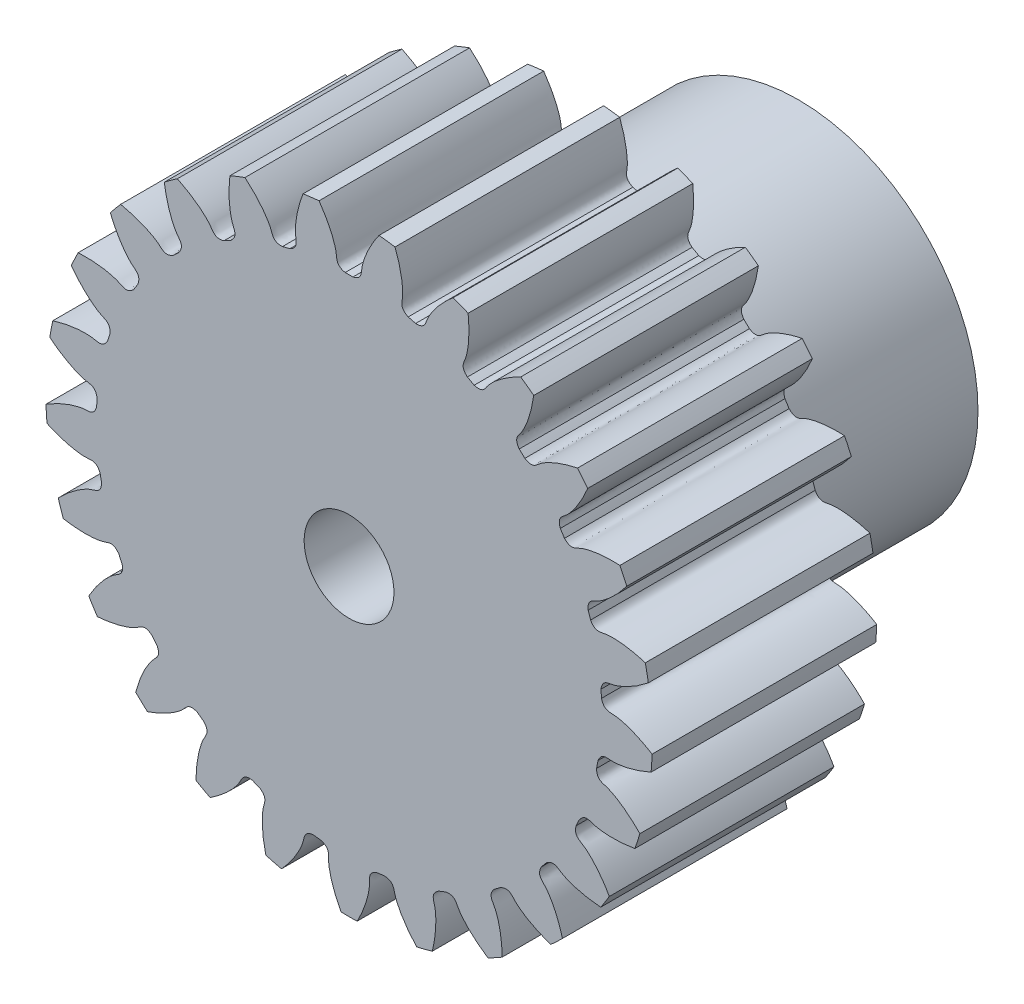
SolidWorks part; units mm, degrees
ref_plane "前视基准面" through (0, 0, 0) normal (0, 0, 1) x (1, 0, 0)
ref_plane "上视基准面" through (0, 0, 0) normal (0, 1, 0) x (1, 0, 0)
ref_plane "右视基准面" through (0, 0, 0) normal (1, 0, 0) x (0, 0, -1)
sketch "草图1" plane through (0, 0, 0) normal (0, 0, 1) x (1, 0, 0)
  circle A0 centre (0, 0) radius 6.75
extrude "凸台-拉伸1" add sketch "草图1" along normal blind 5
ref_axis "基准轴1" through (0, 0, 5) along (0, 0, -1)
sketch "草图2" plane through (0, 0, 0) normal (0, 0, 1) x (1, 0, 0)
  line L0 (0, 0) -> (0, 6.75) construction
  circle A0 centre (0, 0) radius 6.75 construction
  arc A1 (0.086, 5.6243) -> (-0.086, 5.6243) centre (0, 0) ccw
  arc A2 (1.6026, 7.6574) -> (-1.6026, 7.6574) centre (0, 0) ccw
  spline S0 degree 3 poles (0.086, 5.6243) (0.2867, 5.6675) (0.2678, 5.7886) (0.2871, 5.909) (0.2898, 5.9241) (0.2933, 5.9413) (0.2976, 5.9608) (0.3029, 5.9825) (0.3092, 6.0064) (0.3166, 6.0323) (0.3253, 6.0604) (0.3352, 6.0905) (0.3465, 6.1227) (0.3593, 6.1568) (0.3736, 6.1928) (0.3895, 6.2307) (0.4072, 6.2704) (0.4266, 6.3119) (0.4479, 6.3551) (0.4712, 6.3999) (0.4964, 6.4464) (0.5238, 6.4943) (0.5533, 6.5437) (0.585, 6.5946) (0.619, 6.6467) (0.6554, 6.7001) (0.6942, 6.7547) (0.7355, 6.8103) (0.7793, 6.867) (0.8257, 6.9246) (0.8748, 6.9831) (0.9266, 7.0424) (0.9811, 7.1024) (1.0385, 7.1629) (1.0987, 7.224) (1.1618, 7.2855) (1.2278, 7.3473) (1.2968, 7.4094) (1.3687, 7.4716) (1.47, 7.5556) (1.5487, 7.617) (1.6026, 7.6574) knots 0 0 0 0 0.130741 0.135745 0.141658 0.148481 0.156214 0.164857 0.174409 0.184871 0.196243 0.208524 0.221715 0.235816 0.250827 0.266748 0.283578 0.301318 0.319968 0.339527 0.359996 0.381375 0.403664 0.426862 0.450971 0.475988 0.501916 0.528753 0.556501 0.585157 0.614724 0.6452 0.676587 0.708882 0.742088 0.776203 0.811228 0.847163 0.884008 0.921762 1 1 1 1
  spline S1 degree 3 poles (-0.086, 5.6243) (-0.2867, 5.6675) (-0.2678, 5.7886) (-0.2871, 5.909) (-0.2898, 5.9241) (-0.2933, 5.9413) (-0.2976, 5.9608) (-0.3029, 5.9825) (-0.3092, 6.0064) (-0.3166, 6.0323) (-0.3253, 6.0604) (-0.3352, 6.0905) (-0.3465, 6.1227) (-0.3593, 6.1568) (-0.3736, 6.1928) (-0.3895, 6.2307) (-0.4072, 6.2704) (-0.4266, 6.3119) (-0.4479, 6.3551) (-0.4712, 6.3999) (-0.4964, 6.4464) (-0.5238, 6.4943) (-0.5533, 6.5437) (-0.585, 6.5946) (-0.619, 6.6467) (-0.6554, 6.7001) (-0.6942, 6.7547) (-0.7355, 6.8103) (-0.7793, 6.867) (-0.8257, 6.9246) (-0.8748, 6.9831) (-0.9266, 7.0424) (-0.9811, 7.1024) (-1.0385, 7.1629) (-1.0987, 7.224) (-1.1618, 7.2855) (-1.2278, 7.3473) (-1.2968, 7.4094) (-1.3687, 7.4716) (-1.47, 7.5556) (-1.5487, 7.617) (-1.6026, 7.6574) knots 0 0 0 0 0.130741 0.135745 0.141658 0.148481 0.156214 0.164857 0.174409 0.184871 0.196243 0.208524 0.221715 0.235816 0.250827 0.266748 0.283578 0.301318 0.319968 0.339527 0.359996 0.381375 0.403664 0.426862 0.450971 0.475988 0.501916 0.528753 0.556501 0.585157 0.614724 0.6452 0.676587 0.708882 0.742088 0.776203 0.811228 0.847163 0.884008 0.921762 1 1 1 1
extrude "切除-拉伸1" cut sketch "草图2" along normal through all
pattern_circular "阵列(圆周)1" count 25 every 14.4 about axis through (0, 0, 5) along (0, 0, -1) of "切除-拉伸1"
sketch "草图3" plane through (0, 0, 0) normal (0, 0, 1) x (1, 0, 0)
  circle A0 centre (0, 0) radius 6.25 construction
  dimension "Dn" = 12.5
sketch "草图6" plane through (0, 0, 0) normal (0, 0, -1) x (-1, 0, 0)
  circle A0 centre (0, 0) radius 4
  arc A50 (3.0933, -5.9995) -> (3.4081, -5.8264) centre (0, 0) ccw
  arc A51 (3.2363, -4.6008) -> (3.3755, -4.4996) centre (0, 0) ccw
  arc A52 (4.4881, -5.0418) -> (4.75, -4.7958) centre (0, 0) ccw
  arc A53 (4.2788, -3.6514) -> (4.3885, -3.5188) centre (0, 0) ccw
  arc A54 (5.6009, -3.7672) -> (5.7935, -3.4639) centre (0, 0) ccw
  arc A55 (5.0524, -2.4726) -> (5.1257, -2.3169) centre (0, 0) ccw
  arc A56 (6.3618, -2.256) -> (6.4729, -1.9143) centre (0, 0) ccw
  arc A57 (5.5086, -1.1384) -> (5.5408, -0.9694) centre (0, 0) ccw
  arc A58 (6.723, -0.603) -> (6.7456, -0.2444) centre (0, 0) ccw
  arc A59 (5.6186, 0.2673) -> (5.6078, 0.439) centre (0, 0) ccw
  arc A60 (6.6618, 1.0879) -> (6.5944, 1.4408) centre (0, 0) ccw
  arc A61 (5.3757, 1.6562) -> (5.3225, 1.8198) centre (0, 0) ccw
  arc A62 (6.1819, 2.7104) -> (6.0289, 3.0355) centre (0, 0) ccw
  arc A63 (4.7949, 2.941) -> (4.7027, 3.0863) centre (0, 0) ccw
  arc A64 (5.3136, 4.1627) -> (5.0846, 4.4395) centre (0, 0) ccw
  arc A65 (3.9128, 4.0411) -> (3.7874, 4.1589) centre (0, 0) ccw
  arc A66 (4.1115, 5.3533) -> (3.8208, 5.5645) centre (0, 0) ccw
  arc A67 (2.7849, 4.8872) -> (2.6342, 4.9701) centre (0, 0) ccw
  arc A68 (2.651, 6.2076) -> (2.3169, 6.3399) centre (0, 0) ccw
  arc A69 (1.482, 5.4262) -> (1.3154, 5.469) centre (0, 0) ccw
  arc A70 (1.0239, 6.6719) -> (0.6675, 6.7169) centre (0, 0) ccw
  arc A71 (0.086, 5.6243) -> (-0.086, 5.6243) centre (0, 0) ccw
  arc A72 (-0.6675, 6.7169) -> (-1.0239, 6.6719) centre (0, 0) ccw
  arc A73 (-1.3154, 5.469) -> (-1.482, 5.4262) centre (0, 0) ccw
  arc A74 (-2.3169, 6.3399) -> (-2.651, 6.2076) centre (0, 0) ccw
  arc A75 (-2.6342, 4.9701) -> (-2.7849, 4.8872) centre (0, 0) ccw
  arc A76 (-3.8208, 5.5645) -> (-4.1115, 5.3533) centre (0, 0) ccw
  arc A77 (-3.7874, 4.1589) -> (-3.9128, 4.0411) centre (0, 0) ccw
  arc A78 (-5.0846, 4.4395) -> (-5.3136, 4.1627) centre (0, 0) ccw
  arc A79 (-4.7027, 3.0863) -> (-4.7949, 2.941) centre (0, 0) ccw
  arc A80 (-6.0289, 3.0355) -> (-6.1819, 2.7104) centre (0, 0) ccw
  arc A81 (-5.3225, 1.8198) -> (-5.3757, 1.6562) centre (0, 0) ccw
  arc A82 (-6.5944, 1.4408) -> (-6.6618, 1.0879) centre (0, 0) ccw
  arc A83 (-5.6078, 0.439) -> (-5.6186, 0.2673) centre (0, 0) ccw
  arc A84 (-6.7456, -0.2444) -> (-6.723, -0.603) centre (0, 0) ccw
  arc A85 (-5.5408, -0.9694) -> (-5.5086, -1.1384) centre (0, 0) ccw
  arc A86 (-6.4729, -1.9143) -> (-6.3618, -2.256) centre (0, 0) ccw
  arc A87 (-5.1257, -2.3169) -> (-5.0524, -2.4726) centre (0, 0) ccw
  arc A88 (-5.7935, -3.4639) -> (-5.6009, -3.7672) centre (0, 0) ccw
  arc A89 (-4.3885, -3.5188) -> (-4.2788, -3.6514) centre (0, 0) ccw
  arc A90 (-4.75, -4.7958) -> (-4.4881, -5.0418) centre (0, 0) ccw
  arc A91 (-3.3755, -4.4996) -> (-3.2363, -4.6008) centre (0, 0) ccw
  arc A92 (-3.4081, -5.8264) -> (-3.0933, -5.9995) centre (0, 0) ccw
  arc A93 (-2.1504, -5.1977) -> (-1.9905, -5.2611) centre (0, 0) ccw
  arc A94 (-1.8521, -6.4909) -> (-1.5041, -6.5803) centre (0, 0) ccw
  arc A95 (-0.7903, -5.5692) -> (-0.6196, -5.5908) centre (0, 0) ccw
  arc A96 (-0.1797, -6.7476) -> (0.1797, -6.7476) centre (0, 0) ccw
  arc A97 (0.6196, -5.5908) -> (0.7903, -5.5692) centre (0, 0) ccw
  arc A98 (1.5041, -6.5803) -> (1.8521, -6.4909) centre (0, 0) ccw
  arc A99 (1.9905, -5.2611) -> (2.1504, -5.1977) centre (0, 0) ccw
  spline S50 degree 3 poles (-777.3204, -631.6289) (8.1425, 2.0471) (1.5349, -3.862) (2.4452, -5.3934) (2.461, -5.4182) (2.4851, -5.4529) (2.5163, -5.4942) (2.555, -5.5414) (2.6018, -5.5941) (2.6572, -5.6517) (2.7216, -5.7135) (2.7955, -5.779) (2.8792, -5.8473) (11.5445, -12.3671) (53.6939, 27.5793) (-909.7088, -414.3913) knots -1.921213 -1.921213 -1.921213 -1.921213 0.130741 0.135745 0.148481 0.164857 0.184871 0.208524 0.235816 0.266748 0.301318 0.339527 0.381375 0.426862 12.935151 12.935151 12.935151 12.935151 only from (2.1504, -5.1977) to (3.0933, -5.9995)
  spline S51 degree 3 poles (837.1886, 546.2694) (-51.5384, -31.1508) (4.4447, -16.0899) (3.3883, -5.5093) (3.3739, -5.4069) (3.3571, -5.3144) (3.3387, -5.2318) (3.3195, -5.1592) (3.3001, -5.0963) (3.2814, -5.0431) (3.2662, -5.0049) (3.2529, -4.9744) (3.2436, -4.9545) (2.4384, -3.3653) (-6.0906, -5.7778) (949.6878, 317.8279) knots -11.670616 -11.670616 -11.670616 -11.670616 0.596336 0.640004 0.680032 0.716422 0.749173 0.778285 0.803757 0.825591 0.843786 0.851519 0.864255 0.869259 2.921125 2.921125 2.921125 2.921125 only from (3.4081, -5.8264) to (3.2363, -4.6008)
  spline S52 degree 3 poles (-595.8197, -805.0968) (7.3776, 4.0077) (2.4471, -3.3589) (3.7097, -4.6159) (3.7311, -4.636) (3.7631, -4.6636) (3.8036, -4.6958) (3.8528, -4.7319) (3.9113, -4.7714) (3.9792, -4.8133) (4.057, -4.8572) (4.1448, -4.9022) (4.2429, -4.9476) (14.2573, -9.1076) (45.1483, 40.066) (-778.0737, -627.6078) knots -1.921213 -1.921213 -1.921213 -1.921213 0.130741 0.135745 0.148481 0.164857 0.184871 0.208524 0.235816 0.266748 0.301318 0.339527 0.381375 0.426862 12.935151 12.935151 12.935151 12.935151 only from (3.3755, -4.4996) to (4.4881, -5.0418)
  spline S53 degree 3 poles (675.0351, 737.3077) (-42.1723, -42.9892) (8.3064, -14.479) (4.6519, -4.4936) (4.6126, -4.398) (4.5733, -4.3126) (4.535, -4.2372) (4.4982, -4.1716) (4.4638, -4.1155) (4.4324, -4.0686) (4.4082, -4.0354) (4.3878, -4.0091) (4.3739, -3.9922) (3.1987, -2.6532) (-4.4624, -7.111) (840.811, 544.0205) knots -11.670616 -11.670616 -11.670616 -11.670616 0.596336 0.640004 0.680032 0.716422 0.749173 0.778285 0.803757 0.825591 0.843786 0.851519 0.864255 0.869259 2.921125 2.921125 2.921125 2.921125 only from (4.75, -4.7958) to (4.2788, -3.6514)
  spline S54 degree 3 poles (-376.8815, -927.9775) (6.1491, 5.7165) (3.2055, -2.6448) (4.741, -3.5483) (4.7668, -3.5624) (4.8047, -3.5812) (4.8519, -3.6024) (4.9086, -3.6251) (4.975, -3.6488) (5.0513, -3.6725) (5.1375, -3.6957) (5.2337, -3.7174) (5.34, -3.737) (16.0744, -5.2758) (33.7659, 50.0351) (-597.5494, -801.3894) knots -1.921213 -1.921213 -1.921213 -1.921213 0.130741 0.135745 0.148481 0.164857 0.184871 0.208524 0.235816 0.266748 0.301318 0.339527 0.381375 0.426862 12.935151 12.935151 12.935151 12.935151 only from (4.3885, -3.5188) to (5.6009, -3.7672)
  spline S55 degree 3 poles (470.4667, 882.0182) (-30.1564, -52.1264) (11.6462, -11.9584) (5.6233, -3.1955) (5.5614, -3.1127) (5.5021, -3.0397) (5.4462, -2.9762) (5.3943, -2.9218) (5.3471, -2.8761) (5.305, -2.8385) (5.2733, -2.8123) (5.247, -2.792) (5.2293, -2.779) (3.758, -1.7744) (-2.5538, -7.9973) (679.103, 736.0303) knots -11.670616 -11.670616 -11.670616 -11.670616 0.596336 0.640004 0.680032 0.716422 0.749173 0.778285 0.803757 0.825591 0.843786 0.851519 0.864255 0.869259 2.921125 2.921125 2.921125 2.921125 only from (5.7935, -3.4639) to (5.0524, -2.4726)
  spline S56 degree 3 poles (-134.2625, -992.55) (4.5343, 7.0662) (3.7626, -1.7646) (5.4745, -2.2578) (5.503, -2.265) (5.5444, -2.2738) (5.5953, -2.2826) (5.6559, -2.2905) (5.7261, -2.2969) (5.8059, -2.3009) (5.8952, -2.3019) (5.9938, -2.299) (6.1016, -2.2916) (16.8814, -1.1125) (20.2618, 56.8604) (-379.4788, -924.8168) knots -1.921213 -1.921213 -1.921213 -1.921213 0.130741 0.135745 0.148481 0.164857 0.184871 0.208524 0.235816 0.266748 0.301318 0.339527 0.381375 0.426862 12.935151 12.935151 12.935151 12.935151 only from (5.1257, -2.3169) to (6.3618, -2.256)
  spline S57 degree 3 poles (236.3371, 971.3083) (-16.2457, -57.9884) (14.2543, -8.6864) (6.2413, -1.6966) (6.1607, -1.6318) (6.0852, -1.5759) (6.0153, -1.5283) (5.9515, -1.4885) (5.8943, -1.456) (5.8443, -1.43) (5.807, -1.4125) (5.7765, -1.3994) (5.7561, -1.3913) (4.0812, -0.7841) (-0.4847, -8.3812) (474.7244, 881.7926) knots -11.670616 -11.670616 -11.670616 -11.670616 0.596336 0.640004 0.680032 0.716422 0.749173 0.778285 0.803757 0.825591 0.843786 0.851519 0.864255 0.869259 2.921125 2.921125 2.921125 2.921125 only from (6.4729, -1.9143) to (5.5086, -1.1384)
  spline S58 degree 3 poles (116.7928, -994.757) (2.6345, 7.9718) (4.0832, -0.7734) (5.864, -0.8254) (5.8934, -0.8253) (5.9357, -0.8236) (5.9872, -0.8194) (6.0478, -0.812) (6.1174, -0.8007) (6.1957, -0.7848) (6.2824, -0.7635) (6.3772, -0.7362) (6.4798, -0.7022) (16.6277, 3.1207) (5.4847, 60.113) (-137.5642, -990.1345) knots -1.921213 -1.921213 -1.921213 -1.921213 0.130741 0.135745 0.148481 0.164857 0.184871 0.208524 0.235816 0.266748 0.301318 0.339527 0.381375 0.426862 12.935151 12.935151 12.935151 12.935151 only from (5.5408, -0.9694) to (6.723, -0.603)
  spline S59 degree 3 poles (-12.6424, 999.5675) (-1.3142, -60.2067) (15.9667, -4.8686) (6.4672, -0.0912) (6.373, -0.0485) (6.2859, -0.0131) (6.2064, 0.0156) (6.1347, 0.0383) (6.0712, 0.0556) (6.0163, 0.0683) (5.9759, 0.076) (5.943, 0.0811) (5.9212, 0.0839) (4.148, 0.2555) (1.6149, -8.2384) (240.5172, 972.1486) knots -11.670616 -11.670616 -11.670616 -11.670616 0.596336 0.640004 0.680032 0.716422 0.749173 0.778285 0.803757 0.825591 0.843786 0.851519 0.864255 0.869259 2.921125 2.921125 2.921125 2.921125 only from (6.7456, -0.2444) to (5.6186, 0.2673)
  spline S60 degree 3 poles (360.5095, -934.4597) (0.5693, 8.3765) (4.1472, 0.2663) (5.8851, 0.6589) (5.9135, 0.6662) (5.954, 0.6784) (6.0029, 0.6953) (6.0598, 0.7175) (6.1243, 0.7458) (6.1962, 0.7807) (6.2749, 0.8228) (6.36, 0.8729) (6.4509, 0.9314) (15.3293, 7.1578) (-9.6371, 59.5884) (112.9941, -993.2384) knots -1.921213 -1.921213 -1.921213 -1.921213 0.130741 0.135745 0.148481 0.164857 0.184871 0.208524 0.235816 0.266748 0.301318 0.339527 0.381375 0.426862 12.935151 12.935151 12.935151 12.935151 only from (5.6078, 0.439) to (6.6618, 1.0879)
  spline S61 degree 3 poles (-260.8276, 965.0202) (13.6999, -58.642) (16.6758, -0.7449) (6.2867, 1.52) (6.1848, 1.538) (6.0917, 1.5506) (6.0075, 1.5586) (5.9324, 1.5627) (5.8666, 1.5638) (5.8103, 1.5624) (5.7692, 1.5597) (5.7361, 1.5566) (5.7143, 1.5538) (3.9541, 1.2791) (3.6129, -7.578) (-8.8027, 1001.421) knots -11.670616 -11.670616 -11.670616 -11.670616 0.596336 0.640004 0.680032 0.716422 0.749173 0.778285 0.803757 0.825591 0.843786 0.851519 0.864255 0.869259 2.921125 2.921125 2.921125 2.921125 only from (6.5944, 1.4408) to (5.3757, 1.6562)
  spline S62 degree 3 poles (581.5741, -815.4468) (-1.5318, 8.2549) (3.9507, 1.2893) (5.5363, 2.1017) (5.562, 2.1159) (5.5982, 2.1378) (5.6413, 2.1663) (5.6909, 2.202) (5.7465, 2.2454) (5.8074, 2.2971) (5.8732, 2.3575) (5.9431, 2.4271) (6.0166, 2.5064) (13.0676, 10.7451) (-24.1534, 55.3197) (356.4525, -933.9336) knots -1.921213 -1.921213 -1.921213 -1.921213 0.130741 0.135745 0.148481 0.164857 0.184871 0.208524 0.235816 0.266748 0.301318 0.339527 0.381375 0.426862 12.935151 12.935151 12.935151 12.935151 only from (5.3225, 1.8198) to (6.1819, 2.7104)
  spline S63 degree 3 poles (-492.624, 869.8371) (27.8532, -53.3927) (16.3372, 3.4256) (5.7111, 3.0357) (5.6081, 3.0278) (5.5147, 3.0168) (5.4312, 3.0037) (5.3574, 2.989) (5.2934, 2.9736) (5.2392, 2.9582) (5.2001, 2.9455) (5.1688, 2.9342) (5.1484, 2.9261) (3.5118, 2.2222) (5.384, -6.4414) (-257.5694, 967.7703) knots -11.670616 -11.670616 -11.670616 -11.670616 0.596336 0.640004 0.680032 0.716422 0.749173 0.778285 0.803757 0.825591 0.843786 0.851519 0.864255 0.869259 2.921125 2.921125 2.921125 2.921125 only from (6.0289, 3.0355) to (4.7949, 2.941)
  spline S64 degree 3 poles (766.0963, -645.1965) (-3.5366, 7.6147) (3.5059, 2.2313) (4.8397, 3.4125) (4.8611, 3.4327) (4.8907, 3.4629) (4.9254, 3.5012) (4.9645, 3.5481) (5.0075, 3.604) (5.0537, 3.6692) (5.1024, 3.744) (5.1528, 3.8288) (5.2043, 3.9239) (9.9848, 13.6573) (-37.152, 47.575) (577.5137, -815.9462) knots -1.921213 -1.921213 -1.921213 -1.921213 0.130741 0.135745 0.148481 0.164857 0.184871 0.208524 0.235816 0.266748 0.301318 0.339527 0.381375 0.426862 12.935151 12.935151 12.935151 12.935151 only from (4.7027, 3.0863) to (5.3136, 4.1627)
  spline S65 degree 3 poles (-693.467, 719.999) (40.2563, -44.7884) (14.972, 7.3809) (4.7768, 4.3606) (4.6789, 4.3273) (4.5912, 4.2935) (4.5135, 4.26) (4.4458, 4.2274) (4.3876, 4.1966) (4.3389, 4.1682) (4.3042, 4.1462) (4.2767, 4.1274) (4.2589, 4.1146) (2.8488, 3.0258) (6.8168, -4.9001) (-490.1521, 873.3112) knots -11.670616 -11.670616 -11.670616 -11.670616 0.596336 0.640004 0.680032 0.716422 0.749173 0.778285 0.803757 0.825591 0.843786 0.851519 0.864255 0.869259 2.921125 2.921125 2.921125 2.921125 only from (5.0846, 4.4395) to (3.9128, 4.0411)
  spline S66 degree 3 poles (902.4818, -434.406) (-5.3191, 6.4959) (2.8409, 3.0331) (3.839, 4.5089) (3.8547, 4.5337) (3.8759, 4.5703) (3.8999, 4.6161) (3.9262, 4.6713) (3.9539, 4.7361) (3.9824, 4.8107) (4.011, 4.8953) (4.0387, 4.99) (4.0649, 5.0949) (6.2747, 15.7114) (-47.8162, 36.841) (762.2876, -646.6899) knots -1.921213 -1.921213 -1.921213 -1.921213 0.130741 0.135745 0.148481 0.164857 0.184871 0.208524 0.235816 0.266748 0.301318 0.339527 0.381375 0.426862 12.935151 12.935151 12.935151 12.935151 only from (3.7874, 4.1589) to (4.1115, 5.3533)
  spline S67 degree 3 poles (-850.7369, 524.9207) (50.13, -33.37) (12.6661, 10.8724) (3.5423, 5.4115) (3.4558, 5.3549) (3.3792, 5.3004) (3.3123, 5.2486) (3.2548, 5.2002) (3.2061, 5.1559) (3.166, 5.1163) (3.1379, 5.0863) (3.1159, 5.0613) (3.1019, 5.0444) (2.0068, 3.6392) (7.8212, -3.0509) (-691.9367, 723.9786) knots -11.670616 -11.670616 -11.670616 -11.670616 0.596336 0.640004 0.680032 0.716422 0.749173 0.778285 0.803757 0.825591 0.843786 0.851519 0.864255 0.869259 2.921125 2.921125 2.921125 2.921125 only from (3.8208, 5.5645) to (2.7849, 4.8872)
  spline S68 degree 3 poles (982.1611, -196.3203) (-6.7675, 4.969) (1.9973, 3.6443) (2.5971, 5.322) (2.6061, 5.3499) (2.6175, 5.3906) (2.6294, 5.4409) (2.6411, 5.5009) (2.6519, 5.5706) (2.661, 5.6499) (2.6675, 5.739) (2.6709, 5.8376) (2.6702, 5.9457) (2.1703, 16.7783) (-55.476, 23.7922) (899.1642, -436.7997) knots -1.921213 -1.921213 -1.921213 -1.921213 0.130741 0.135745 0.148481 0.164857 0.184871 0.208524 0.235816 0.266748 0.301318 0.339527 0.381375 0.426862 12.935151 12.935151 12.935151 12.935151 only from (2.6342, 4.9701) to (2.651, 6.2076)
  spline S69 degree 3 poles (-954.5519, 296.8597) (56.8539, -19.8548) (9.5643, 13.6807) (2.0852, 6.1225) (2.0155, 6.0461) (1.9549, 5.9743) (1.903, 5.9074) (1.8593, 5.8463) (1.8232, 5.7913) (1.7941, 5.7429) (1.7744, 5.7069) (1.7593, 5.6772) (1.7499, 5.6574) (1.0388, 4.0239) (8.3342, -1.01) (-850.2444, 529.1559) knots -11.670616 -11.670616 -11.670616 -11.670616 0.596336 0.640004 0.680032 0.716422 0.749173 0.778285 0.803757 0.825591 0.843786 0.851519 0.864255 0.869259 2.921125 2.921125 2.921125 2.921125 only from (2.3169, 6.3399) to (1.482, 5.4262)
  spline S70 degree 3 poles (1000.1275, 54.101) (-7.7906, 3.1299) (1.0283, 4.0266) (1.192, 5.8006) (1.1938, 5.8299) (1.1947, 5.8722) (1.1937, 5.9239) (1.1901, 5.9849) (1.1833, 6.0551) (1.1723, 6.1342) (1.1565, 6.2221) (1.1352, 6.3184) (1.1077, 6.423) (-2.0704, 16.7909) (-59.65, 9.2484) (979.543, -199.4638) knots -1.921213 -1.921213 -1.921213 -1.921213 0.130741 0.135745 0.148481 0.164857 0.184871 0.208524 0.235816 0.266748 0.301318 0.339527 0.381375 0.426862 12.935151 12.935151 12.935151 12.935151 only from (1.3154, 5.469) to (1.0239, 6.6719)
  spline S71 degree 3 poles (-998.3889, 50.1459) (60.0054, -5.092) (5.8616, 15.6295) (0.4971, 6.4487) (0.4485, 6.3574) (0.4077, 6.2727) (0.3741, 6.1951) (0.347, 6.125) (0.3257, 6.0627) (0.3096, 6.0087) (0.2994, 5.9688) (0.2922, 5.9364) (0.288, 5.9148) (0.0054, 4.1559) (8.3235, 1.0944) (-955.1281, 301.0843) knots -11.670616 -11.670616 -11.670616 -11.670616 0.596336 0.640004 0.680032 0.716422 0.749173 0.778285 0.803757 0.825591 0.843786 0.851519 0.864255 0.869259 2.921125 2.921125 2.921125 2.921125 only from (0.6675, 6.7169) to (0.086, 5.6243)
  spline S72 degree 3 poles (955.2523, 301.1229) (-8.3243, 1.0941) (-0.0054, 4.1558) (-0.288, 5.9148) (-0.2936, 5.9437) (-0.3032, 5.9848) (-0.317, 6.0347) (-0.3356, 6.0929) (-0.3598, 6.1591) (-0.3901, 6.233) (-0.4272, 6.3142) (-0.4718, 6.4022) (-0.5245, 6.4966) (-6.1811, 15.7485) (-60.0759, -5.8765) (998.3735, 50.4051) knots -1.921213 -1.921213 -1.921213 -1.921213 0.130741 0.135745 0.148481 0.164857 0.184871 0.208524 0.235816 0.266748 0.301318 0.339527 0.381375 0.426862 12.935151 12.935151 12.935151 12.935151 only from (-0.086, 5.6243) to (-0.6675, 6.7169)
  spline S73 degree 3 poles (-979.4935, -199.7188) (59.3865, 9.9907) (1.7905, 16.5962) (-1.1222, 6.3697) (-1.1466, 6.2692) (-1.165, 6.1771) (-1.1783, 6.0935) (-1.1872, 6.0188) (-1.1923, 5.9533) (-1.1945, 5.8969) (-1.1944, 5.8558) (-1.1933, 5.8225) (-1.192, 5.8006) (-1.0283, 4.0266) (7.7899, 3.13) (-999.9976, 54.0945) knots -11.670616 -11.670616 -11.670616 -11.670616 0.596336 0.640004 0.680032 0.716422 0.749173 0.778285 0.803757 0.825591 0.843786 0.851519 0.864255 0.869259 2.921125 2.921125 2.921125 2.921125 only from (-1.0239, 6.6719) to (-1.3154, 5.469)
  spline S74 degree 3 poles (850.3551, 529.2242) (-8.3348, -1.0104) (-1.0387, 4.0239) (-1.7499, 5.6574) (-1.7625, 5.6839) (-1.7821, 5.7214) (-1.8078, 5.7662) (-1.8403, 5.818) (-1.8802, 5.8761) (-1.9279, 5.9402) (-1.9841, 6.0096) (-2.0492, 6.0838) (-2.1236, 6.1621) (-9.9034, 13.7165) (-56.7271, -20.6322) (954.4725, 297.107) knots -1.921213 -1.921213 -1.921213 -1.921213 0.130741 0.135745 0.148481 0.164857 0.184871 0.208524 0.235816 0.266748 0.301318 0.339527 0.381375 0.426862 12.935151 12.935151 12.935151 12.935151 only from (-1.482, 5.4262) to (-2.3169, 6.3399)
  spline S75 degree 3 poles (-899.0528, -437.0344) (55.0362, 24.4457) (-2.393, 16.52) (-2.6711, 5.8905) (-2.6696, 5.7871) (-2.6646, 5.6933) (-2.6567, 5.609) (-2.6467, 5.5345) (-2.6354, 5.4697) (-2.6234, 5.4146) (-2.6131, 5.3748) (-2.6038, 5.3428) (-2.5971, 5.322) (-1.9974, 3.6444) (6.7668, 4.9689) (-982.0336, -196.2943) knots -11.670616 -11.670616 -11.670616 -11.670616 0.596336 0.640004 0.680032 0.716422 0.749173 0.778285 0.803757 0.825591 0.843786 0.851519 0.864255 0.869259 2.921125 2.921125 2.921125 2.921125 only from (-2.651, 6.2076) to (-2.6342, 4.9701)
  spline S76 degree 3 poles (692.0269, 724.0724) (-7.8217, -3.0515) (-2.0068, 3.6391) (-3.1019, 5.0444) (-3.1207, 5.067) (-3.149, 5.0985) (-3.185, 5.1355) (-3.2294, 5.1775) (-3.2824, 5.2239) (-3.3446, 5.2741) (-3.4163, 5.3274) (-3.4977, 5.383) (-3.5894, 5.4404) (-13.0034, 10.8227) (-49.8139, -34.0914) (850.5985, 525.1405) knots -1.921213 -1.921213 -1.921213 -1.921213 0.130741 0.135745 0.148481 0.164857 0.184871 0.208524 0.235816 0.266748 0.301318 0.339527 0.381375 0.426862 12.935151 12.935151 12.935151 12.935151 only from (-2.7849, 4.8872) to (-3.8208, 5.5645)
  spline S77 degree 3 poles (-762.1214, -646.8895) (47.2278, 37.3646) (-6.4262, 15.4059) (-4.0521, 5.0412) (-4.025, 4.9414) (-3.9967, 4.8517) (-3.9681, 4.7721) (-3.9399, 4.7024) (-3.9128, 4.6425) (-3.8876, 4.5921) (-3.8677, 4.5561) (-3.8507, 4.5274) (-3.839, 4.5089) (-2.8409, 3.0332) (5.3184, 6.4956) (-902.3648, -434.3492) knots -11.670616 -11.670616 -11.670616 -11.670616 0.596336 0.640004 0.680032 0.716422 0.749173 0.778285 0.803757 0.825591 0.843786 0.851519 0.864255 0.869259 2.921125 2.921125 2.921125 2.921125 only from (-4.1115, 5.3533) to (-3.7874, 4.1589)
  spline S78 degree 3 poles (490.2161, 873.4244) (-6.8171, -4.9008) (-2.8488, 3.0257) (-4.2589, 4.1146) (-4.2827, 4.1318) (-4.318, 4.1552) (-4.3621, 4.1821) (-4.4155, 4.2117) (-4.4784, 4.2435) (-4.5511, 4.2767) (-4.6338, 4.3104) (-4.7266, 4.3441) (-4.8296, 4.3768) (-15.2864, 7.2489) (-39.7707, -45.4086) (693.2782, 720.1774) knots -1.921213 -1.921213 -1.921213 -1.921213 0.130741 0.135745 0.148481 0.164857 0.184871 0.208524 0.235816 0.266748 0.301318 0.339527 0.381375 0.426862 12.935151 12.935151 12.935151 12.935151 only from (-3.9128, 4.0411) to (-5.0846, 4.4395)
  spline S79 degree 3 poles (-577.3031, -816.0981) (36.4518, 47.9358) (-10.0556, 13.3238) (-5.1784, 3.8751) (-5.1274, 3.7852) (-5.0778, 3.7054) (-5.0303, 3.6354) (-4.9856, 3.5749) (-4.9444, 3.5236) (-4.9074, 3.481) (-4.8792, 3.4511) (-4.8557, 3.4276) (-4.8397, 3.4125) (-3.506, 2.2314) (3.536, 7.6142) (-765.9971, -645.1123) knots -11.670616 -11.670616 -11.670616 -11.670616 0.596336 0.640004 0.680032 0.716422 0.749173 0.778285 0.803757 0.825591 0.843786 0.851519 0.864255 0.869259 2.921125 2.921125 2.921125 2.921125 only from (-5.3136, 4.1627) to (-4.7027, 3.0863)
  spline S80 degree 3 poles (257.6033, 967.8959) (-5.3842, -6.4421) (-3.5117, 2.2222) (-5.1484, 2.9261) (-5.1757, 2.9369) (-5.2157, 2.9508) (-5.2651, 2.9659) (-5.3242, 2.9813) (-5.3931, 2.9965) (-5.4717, 3.0105) (-5.5602, 3.0226) (-5.6584, 3.0321) (-5.7663, 3.0383) (-16.6089, 3.2196) (-27.2286, -53.8726) (492.3968, 869.963) knots -1.921213 -1.921213 -1.921213 -1.921213 0.130741 0.135745 0.148481 0.164857 0.184871 0.208524 0.235816 0.266748 0.301318 0.339527 0.381375 0.426862 12.935151 12.935151 12.935151 12.935151 only from (-4.7949, 2.941) to (-6.0289, 3.0355)
  spline S81 degree 3 poles (-356.2107, -934.0283) (23.3855, 55.495) (-13.0532, 10.4044) (-5.9794, 2.4655) (-5.9076, 2.3911) (-5.8397, 2.3262) (-5.7763, 2.2702) (-5.718, 2.2227) (-5.6654, 2.1832) (-5.6189, 2.1512) (-5.5842, 2.1292) (-5.5555, 2.1123) (-5.5363, 2.1017) (-3.9508, 1.2894) (1.5313, 8.2543) (-581.499, -815.3406) knots -11.670616 -11.670616 -11.670616 -11.670616 0.596336 0.640004 0.680032 0.716422 0.749173 0.778285 0.803757 0.825591 0.843786 0.851519 0.864255 0.869259 2.921125 2.921125 2.921125 2.921125 only from (-6.1819, 2.7104) to (-5.3225, 1.8198)
  spline S82 degree 3 poles (8.8043, 1001.551) (-3.6129, -7.5787) (-3.9541, 1.2791) (-5.7143, 1.5538) (-5.7435, 1.5575) (-5.7856, 1.561) (-5.8373, 1.5633) (-5.8984, 1.5636) (-5.9688, 1.5611) (-6.0485, 1.5551) (-6.1372, 1.5449) (-6.2347, 1.5297) (-6.3407, 1.5088) (-16.8877, -1.0121) (-12.9756, -58.9516) (260.5762, 965.0856) knots -1.921213 -1.921213 -1.921213 -1.921213 0.130741 0.135745 0.148481 0.164857 0.184871 0.208524 0.235816 0.266748 0.301318 0.339527 0.381375 0.426862 12.935151 12.935151 12.935151 12.935151 only from (-5.3757, 1.6562) to (-6.5944, 1.4408)
  spline S83 degree 3 poles (-112.7363, -993.2701) (8.8497, 59.5673) (-15.2306, 6.8314) (-6.4047, 0.901) (-6.3167, 0.8468) (-6.2347, 0.8008) (-6.1594, 0.7623) (-6.0911, 0.7309) (-6.0303, 0.7057) (-5.9774, 0.6862) (-5.9383, 0.6736) (-5.9063, 0.6644) (-5.8851, 0.6589) (-4.1473, 0.2664) (-0.5696, 8.3758) (-360.4631, -934.3381) knots -11.670616 -11.670616 -11.670616 -11.670616 0.596336 0.640004 0.680032 0.716422 0.749173 0.778285 0.803757 0.825591 0.843786 0.851519 0.864255 0.869259 2.921125 2.921125 2.921125 2.921125 only from (-6.6618, 1.0879) to (-5.6078, 0.439)
  spline S84 degree 3 poles (-240.548, 972.275) (-1.6146, -8.2391) (-4.1479, 0.2555) (-5.9212, 0.0839) (-5.9504, 0.0802) (-5.9921, 0.0731) (-6.0427, 0.0625) (-6.1019, 0.0476) (-6.1695, 0.0277) (-6.2452, 0.0021) (-6.3286, -0.0299) (-6.4192, -0.0689) (-6.5167, -0.1155) (-16.1055, -5.1801) (2.0927, -60.3264) (12.3827, 999.5684) knots -1.921213 -1.921213 -1.921213 -1.921213 0.130741 0.135745 0.148481 0.164857 0.184871 0.208524 0.235816 0.266748 0.301318 0.339527 0.381375 0.426862 12.935151 12.935151 12.935151 12.935151 only from (-5.6186, 0.2673) to (-6.7456, -0.2444)
  spline S85 degree 3 poles (137.8218, -990.1011) (-6.2421, 59.8967) (-16.451, 2.8291) (-6.4276, -0.7201) (-6.3288, -0.7507) (-6.238, -0.7749) (-6.1555, -0.7934) (-6.0815, -0.8069) (-6.0164, -0.8161) (-5.9603, -0.8218) (-5.9192, -0.8244) (-5.886, -0.8254) (-5.864, -0.8254) (-4.0833, -0.7734) (-2.6347, 7.971) (-116.7781, -994.6277) knots -11.670616 -11.670616 -11.670616 -11.670616 0.596336 0.640004 0.680032 0.716422 0.749173 0.778285 0.803757 0.825591 0.843786 0.851519 0.864255 0.869259 2.921125 2.921125 2.921125 2.921125 only from (-6.723, -0.603) to (-5.5408, -0.9694)
  spline S86 degree 3 poles (-474.7857, 881.9074) (0.4851, -8.3818) (-4.0812, -0.784) (-5.7561, -1.3913) (-5.7834, -1.4021) (-5.822, -1.4193) (-5.8684, -1.4422) (-5.922, -1.4714) (-5.9826, -1.5075) (-6.0495, -1.5511) (-6.1223, -1.6028) (-6.2004, -1.6631) (-6.2833, -1.7325) (-14.3113, -9.0226) (17.0295, -57.9107) (-236.5889, 971.2446) knots -1.921213 -1.921213 -1.921213 -1.921213 0.130741 0.135745 0.148481 0.164857 0.184871 0.208524 0.235816 0.266748 0.301318 0.339527 0.381375 0.426862 12.935151 12.935151 12.935151 12.935151 only from (-5.5086, -1.1384) to (-6.4729, -1.9143)
  spline S87 degree 3 poles (379.72, -924.7204) (-20.9417, 56.4626) (-16.6377, -1.351) (-6.0466, -2.2959) (-5.9433, -2.301) (-5.8493, -2.3019) (-5.7648, -2.2993) (-5.6898, -2.294) (-5.6244, -2.2867) (-5.5686, -2.2783) (-5.5283, -2.2705) (-5.4958, -2.2632) (-5.4745, -2.2578) (-3.7626, -1.7646) (-4.5342, 7.0654) (134.2446, -992.4212) knots -11.670616 -11.670616 -11.670616 -11.670616 0.596336 0.640004 0.680032 0.716422 0.749173 0.778285 0.803757 0.825591 0.843786 0.851519 0.864255 0.869259 2.921125 2.921125 2.921125 2.921125 only from (-6.3618, -2.256) to (-5.1257, -2.3169)
  spline S88 degree 3 poles (-679.1908, 736.1262) (2.5543, -7.9979) (-3.758, -1.7743) (-5.2293, -2.779) (-5.253, -2.7963) (-5.2861, -2.8226) (-5.3253, -2.8563) (-5.3701, -2.8979) (-5.4197, -2.9479) (-5.4737, -3.0068) (-5.5314, -3.075) (-5.592, -3.1528) (-5.655, -3.2407) (-11.6178, -12.2982) (30.8963, -51.8562) (-470.6947, 881.8939) knots -1.921213 -1.921213 -1.921213 -1.921213 0.130741 0.135745 0.148481 0.164857 0.184871 0.208524 0.235816 0.266748 0.301318 0.339527 0.381375 0.426862 12.935151 12.935151 12.935151 12.935151 only from (-5.0524, -2.4726) to (-5.7935, -3.4639)
  spline S89 degree 3 poles (597.759, -801.2361) (-34.3254, 49.4807) (-15.779, -5.4462) (-5.2856, -3.7275) (-5.1844, -3.7068) (-5.0931, -3.6842) (-5.0119, -3.6607) (-4.9405, -3.6369) (-4.879, -3.6136) (-4.8271, -3.5916) (-4.7899, -3.574) (-4.7603, -3.5588) (-4.741, -3.5483) (-3.2056, -2.6449) (-6.1489, 5.7158) (376.8321, -927.8572) knots -11.670616 -11.670616 -11.670616 -11.670616 0.596336 0.640004 0.680032 0.716422 0.749173 0.778285 0.803757 0.825591 0.843786 0.851519 0.864255 0.869259 2.921125 2.921125 2.921125 2.921125 only from (-5.6009, -3.7672) to (-4.3885, -3.5188)
  spline S90 degree 3 poles (-840.92, 544.0916) (4.463, -7.1114) (-3.1986, -2.6532) (-4.3739, -3.9922) (-4.3925, -4.0149) (-4.4181, -4.0485) (-4.4477, -4.0909) (-4.4807, -4.1423) (-4.5163, -4.2031) (-4.554, -4.2736) (-4.5929, -4.354) (-4.6323, -4.4445) (-4.6714, -4.5452) (-8.1944, -14.8011) (42.8218, -42.5435) (-675.225, 737.1305) knots -1.921213 -1.921213 -1.921213 -1.921213 0.130741 0.135745 0.148481 0.164857 0.184871 0.208524 0.235816 0.266748 0.301318 0.339527 0.381375 0.426862 12.935151 12.935151 12.935151 12.935151 only from (-4.2788, -3.6514) to (-4.75, -4.7958)
  spline S91 degree 3 poles (778.2386, -627.4071) (-45.5524, 39.3898) (-13.9289, -9.1992) (-4.1926, -4.9249) (-4.0997, -4.8796) (-4.0169, -4.8351) (-3.944, -4.7921) (-3.8809, -4.7513) (-3.8271, -4.7134) (-3.7823, -4.6792) (-3.7506, -4.6529) (-3.7257, -4.6309) (-3.7097, -4.6159) (-2.4471, -3.359) (-7.3771, 4.0071) (595.742, -804.9925) knots -11.670616 -11.670616 -11.670616 -11.670616 0.596336 0.640004 0.680032 0.716422 0.749173 0.778285 0.803757 0.825591 0.843786 0.851519 0.864255 0.869259 2.921125 2.921125 2.921125 2.921125 only from (-4.4881, -5.0418) to (-3.3755, -4.4996)
  spline S92 degree 3 poles (-949.811, 317.8696) (6.0914, -5.778) (-2.4383, -3.3653) (-3.2436, -4.9545) (-3.2561, -4.9811) (-3.2725, -5.0201) (-3.2906, -5.0685) (-3.3098, -5.1265) (-3.3292, -5.1943) (-3.3481, -5.2719) (-3.3658, -5.3594) (-3.3814, -5.4568) (-3.3943, -5.5642) (-4.2561, -16.3739) (52.0566, -30.5575) (-837.3285, 546.0506) knots -1.921213 -1.921213 -1.921213 -1.921213 0.130741 0.135745 0.148481 0.164857 0.184871 0.208524 0.235816 0.266748 0.301318 0.339527 0.381375 0.426862 12.935151 12.935151 12.935151 12.935151 only from (-3.2363, -4.6008) to (-3.4081, -5.8264)
  spline S93 degree 3 poles (909.8186, -414.1559) (-53.9171, 26.8239) (-11.2035, -12.3741) (-2.8361, -5.8128) (-2.7573, -5.7458) (-2.6883, -5.6821) (-2.6284, -5.6224) (-2.5774, -5.5671) (-2.5346, -5.5171) (-2.4998, -5.4728) (-2.4757, -5.4395) (-2.457, -5.4119) (-2.4452, -5.3934) (-1.5349, -3.862) (-8.1419, 2.0466) (777.2191, -631.5472) knots -11.670616 -11.670616 -11.670616 -11.670616 0.596336 0.640004 0.680032 0.716422 0.749173 0.778285 0.803757 0.825591 0.843786 0.851519 0.864255 0.869259 2.921125 2.921125 2.921125 2.921125 only from (-3.0933, -5.9995) to (-2.1504, -5.1977)
  spline S94 degree 3 poles (-999.0219, 71.6748) (7.3369, -4.0816) (-1.5248, -3.8659) (-1.9096, -5.6055) (-1.915, -5.6344) (-1.9212, -5.6762) (-1.9268, -5.7276) (-1.9309, -5.7885) (-1.9328, -5.859) (-1.9319, -5.9389) (-1.9272, -6.0281) (-1.9181, -6.1263) (-1.9039, -6.2335) (-0.0503, -16.918) (58.0205, -16.6516) (-946.8196, 320.6603) knots -1.921213 -1.921213 -1.921213 -1.921213 0.130741 0.135745 0.148481 0.164857 0.184871 0.208524 0.235816 0.266748 0.301318 0.339527 0.381375 0.426862 12.935151 12.935151 12.935151 12.935151 only from (-1.9905, -5.2611) to (-1.8521, -6.4909)
  spline S95 degree 3 poles (984.2314, -174.8818) (-58.894, 12.5725) (-7.7742, -14.7716) (-1.3014, -6.3355) (-1.2418, -6.2511) (-1.1907, -6.1722) (-1.1476, -6.0994) (-1.1119, -6.0332) (-1.083, -5.9741) (-1.0602, -5.9225) (-1.0451, -5.8843) (-1.0339, -5.8529) (-1.0271, -5.8321) (-0.5262, -4.1224) (-8.3951, -0.0425) (909.8608, -418.4194) knots -11.670616 -11.670616 -11.670616 -11.670616 0.596336 0.640004 0.680032 0.716422 0.749173 0.778285 0.803757 0.825591 0.843786 0.851519 0.864255 0.869259 2.921125 2.921125 2.921125 2.921125 only from (-1.5041, -6.5803) to (-0.7903, -5.5692)
  spline S96 degree 3 poles (-985.4606, -179.0236) (8.1215, -2.1288) (-0.5155, -4.1237) (-0.4556, -5.9043) (-0.4537, -5.9336) (-0.4492, -5.9757) (-0.4418, -6.0268) (-0.4307, -6.0869) (-0.415, -6.1556) (-0.3942, -6.2327) (-0.3675, -6.318) (-0.3343, -6.4109) (-0.2939, -6.5111) (4.1586, -16.399) (60.3387, -1.6993) (-996.8184, 75.1217) knots -1.921213 -1.921213 -1.921213 -1.921213 0.130741 0.135745 0.148481 0.164857 0.184871 0.208524 0.235816 0.266748 0.301318 0.339527 0.381375 0.426862 12.935151 12.935151 12.935151 12.935151 only from (-0.6196, -5.5908) to (-0.1797, -6.7476)
  spline S97 degree 3 poles (996.8013, 75.3808) (-60.1704, -2.4688) (-3.8564, -16.2409) (0.3151, -6.4601) (0.3518, -6.3635) (0.3817, -6.2744) (0.4053, -6.1931) (0.4234, -6.1202) (0.4368, -6.0557) (0.446, -6.0001) (0.4511, -5.9593) (0.4541, -5.9262) (0.4556, -5.9043) (0.5155, -4.1238) (-8.1207, -2.129) (985.3325, -179.0008) knots -11.670616 -11.670616 -11.670616 -11.670616 0.596336 0.640004 0.680032 0.716422 0.749173 0.778285 0.803757 0.825591 0.843786 0.851519 0.864255 0.869259 2.921125 2.921125 2.921125 2.921125 only from (0.1797, -6.7476) to (0.6196, -5.5908)
  spline S98 degree 3 poles (-909.9791, -418.4734) (8.3957, -0.0422) (0.5262, -4.1223) (1.0271, -5.8321) (1.0362, -5.86) (1.051, -5.8996) (1.0709, -5.9473) (1.0966, -6.0027) (1.1289, -6.0654) (1.1682, -6.135) (1.2152, -6.2109) (1.2705, -6.2926) (1.3346, -6.3797) (8.1062, -14.8496) (58.8657, 13.3597) (-984.1836, -175.1371) knots -1.921213 -1.921213 -1.921213 -1.921213 0.130741 0.135745 0.148481 0.164857 0.184871 0.208524 0.235816 0.266748 0.301318 0.339527 0.381375 0.426862 12.935151 12.935151 12.935151 12.935151 only from (0.7903, -5.5692) to (1.5041, -6.5803)
  spline S99 degree 3 poles (3797.3062, 1255.3753) (-139.154, -15.0832) (-0.5839, -22.4914) (1.9117, -6.1788) (1.9233, -6.0761) (1.93, -5.9823) (1.9328, -5.8978) (1.9322, -5.8226) (1.929, -5.7569) (1.9241, -5.7007) (1.9189, -5.6599) (1.9137, -5.627) (1.9096, -5.6055) (1.3028, -2.862) (-20.488, -4.9879) (3990.3368, 296.5641) knots -18.487765 -18.487765 -18.487765 -18.487765 0.596336 0.640004 0.680032 0.716422 0.749173 0.778285 0.803757 0.825591 0.843786 0.851519 0.864255 0.869259 4.115666 4.115666 4.115666 4.115666 only from (1.8521, -6.4909) to (1.9905, -5.2611)
  spline S149 degree 3 poles (1.8521, -6.4909) (1.8684, -6.4235) (1.8903, -6.3187) (1.9117, -6.1788) (1.9233, -6.0761) (1.93, -5.9823) (1.9328, -5.8978) (1.9322, -5.8226) (1.929, -5.7569) (1.9241, -5.7007) (1.9189, -5.6599) (1.9137, -5.627) (1.9096, -5.6055) (1.882, -5.4807) (1.8198, -5.3751) (1.9905, -5.2611) knots 0.51569 0.51569 0.51569 0.51569 0.596336 0.640004 0.680032 0.716422 0.749173 0.778285 0.803757 0.825591 0.843786 0.851519 0.864255 0.869259 1 1 1 1
  dimension "D2" = 8
  dimension "D1" = 0
extrude "凸台-拉伸2" add sketch "草图6" along normal blind 5 contours A0 region at (0, 0, 0)
sketch "草图7" plane through (0, 0, -5) normal (0, 0, -1) x (-1, 0, 0)
  circle A0 centre (0, 0) radius 1
  dimension "D1" = 2
extrude "切除-拉伸3" cut sketch "草图7" against normal blind 16
